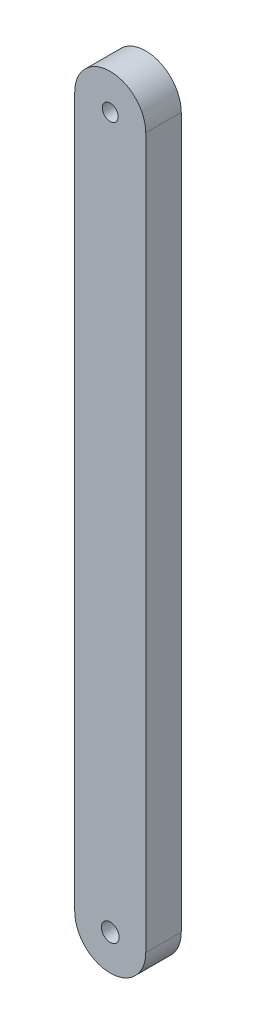
SolidWorks part; units mm, degrees
ref_plane "Front Plane" through (0, 0, 0) normal (0, 0, 1) x (1, 0, 0)
ref_plane "Top Plane" through (0, 0, 0) normal (0, 1, 0) x (1, 0, 0)
ref_plane "Right Plane" through (0, 0, 0) normal (1, 0, 0) x (0, 0, -1)
sketch "Sketch1" plane through (0, 0, 0) normal (0, 1, 0) x (1, 0, 0)
  line L0 (-10, 100) -> (10, 100) construction
  line L2 (10, -100) -> (10, 100)
  line L4 (-10, -100) -> (-10, 100)
  line L5 (10, -100) -> (-10, 100) construction
  line L6 (10, 100) -> (-10, -100) construction
  line L8 (-1.5875, 98.4125) -> (1.5875, 98.4125)
  line L9 (-1.5875, 98.4125) -> (-1.5875, 101.5875)
  line L10 (-1.5875, 101.5875) -> (1.5875, 101.5875)
  line L11 (1.5875, 98.4125) -> (1.5875, 101.5875)
  line L12 (-1.5875, 98.4125) -> (1.5875, 101.5875) construction
  line L13 (-1.5875, 101.5875) -> (1.5875, 98.4125) construction
  arc A0 (-10, 100) -> (10, 100) centre (0, 100) cw
  arc A1 (10, -100) -> (-10, -100) centre (0, -100) cw
  circle A2 centre (0, -100) radius 2.5
  circle A3 centre (0, 100) radius 2.2451
  point P0 (0, 0)
  dimension "D3" = 5
  dimension "D1" = 200
  dimension "D2" = 20
  dimension "D4" = 3.175
extrude "Boss-Extrude1" add sketch "Sketch1" along normal blind 10 contours A1 L2 A0 L4 A3 A2 region at (0, 0, -0.0888)
move or copy body "Body-Move/Copy1" bodies to move or copy 101 copy no rotation origin (0, 5, 0) rotation axis (1, 0, 0) rotation angle 90
move or copy body "Body-Move/Copy2" bodies to move or copy 104 copy no translate (0, -105, 0)
